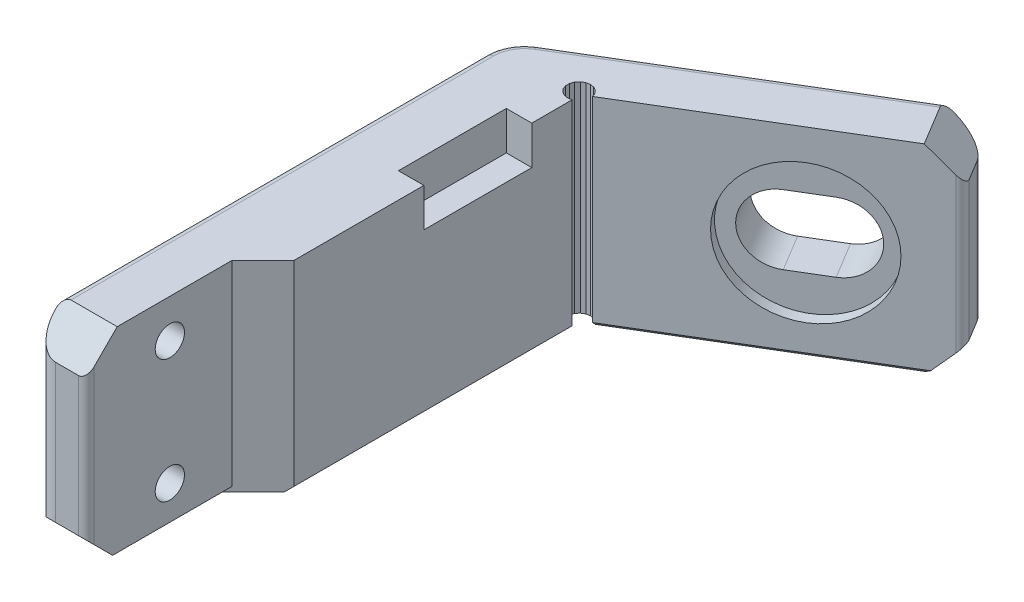
SolidWorks part; units mm, degrees
ref_plane "Front Plane" through (0, 0, 0) normal (0, 0, 1) x (1, 0, 0)
ref_plane "Top Plane" through (0, 0, 0) normal (0, 1, 0) x (1, 0, 0)
ref_plane "Right Plane" through (0, 0, 0) normal (1, 0, 0) x (0, 0, -1)
ref_plane "PY -20.700" through (0, -20.7, 0) normal (0, 1, 0) x (1, 0, 0)
sketch "leg and pad sketch" plane through (0, -20.7, 0) normal (0, 1, 0) x (1, 0, 0)
  line L0 (0.5513, 30.3327) -> (0.3673, 30.8194)
  line L1 (0.3673, 30.8194) -> (0.028, 31.2139)
  line L2 (0.028, 31.2139) -> (-0.4256, 31.4688)
  line L3 (-0.4256, 31.4688) -> (-0.939, 31.5534)
  line L4 (-0.939, 31.5534) -> (-1.4504, 31.4576)
  line L5 (-1.4504, 31.4576) -> (-1.8983, 31.1928)
  line L6 (-1.8983, 31.1928) -> (-2.2288, 30.7909)
  line L7 (-2.2288, 30.7909) -> (-2.4021, 30.3003)
  line L8 (-2.4021, 30.3003) -> (-2.3973, 29.78)
  line L9 (-2.3973, 29.78) -> (-2.2152, 29.2926)
  line L10 (-2.2152, 29.2926) -> (-1.8775, 28.8968)
  line L11 (-1.8775, 28.8968) -> (-1.4248, 28.6402)
  line L12 (-1.4248, 28.6402) -> (-0.9118, 28.5536)
  line L13 (-0.9118, 28.5536) -> (-0.4, 28.6475)
  line L14 (-0.4, 28.6475) -> (-0.4, -7.48)
  line L15 (-0.4, -7.48) -> (-4.42, -11.5)
  line L16 (-4.42, -11.5) -> (-4.42, -30.37)
  line L17 (-4.42, -30.37) -> (-11.42, -30.37)
  line L18 (-11.42, -30.37) -> (-11.42, 31.2838)
  line L19 (-11.42, 31.2838) -> (27.2048, 54.5947)
  line L20 (27.2048, 54.5947) -> (30.8218, 48.6015)
  line L21 (30.8218, 48.6015) -> (0.5513, 30.3327)
extrude "leg and pad" add sketch "leg and pad sketch" along normal mid plane 26
ref_plane "PX -1.350" through (-1.35, 0, 0) normal (1, 0, 0) x (0, 0, -1)
sketch "screw head relief sketch" plane through (-1.35, 0, 0) normal (1, 0, 0) x (0, 0, -1)
  line L0 (23.4, -12.7) -> (23.4, -6.7)
  line L1 (23.4, -6.7) -> (9.4, -6.7)
  line L2 (9.4, -6.7) -> (9.4, -12.7)
  line L3 (9.4, -12.7) -> (23.4, -12.7)
extrude "screw head relief" cut sketch "screw head relief sketch" against normal mid plane 4.7
sketch "insert flange relief sketch" plane through (0, -20.7, 0) normal (0, 1, 0) x (1, 0, 0)
  line L0 (18.3249, 39.8914) -> (17.0331, 42.0318)
  line L1 (17.0331, 42.0318) -> (9.3276, 37.3814)
  line L2 (9.3276, 37.3814) -> (10.6194, 35.241)
  line L3 (10.6194, 35.241) -> (18.3249, 39.8914)
revolve "insert flange relief" cut sketch "insert flange relief sketch" angle 360 about L0
sketch "M6 slot end 1 sketch" plane through (0, -20.7, 0) normal (0, 1, 0) x (1, 0, 0)
  line L0 (20.4653, 41.1832) -> (15.8149, 48.8886)
  line L1 (15.8149, 48.8886) -> (11.9621, 46.5634)
  line L2 (11.9621, 46.5634) -> (16.6125, 38.858)
  line L3 (16.6125, 38.858) -> (20.4653, 41.1832)
revolve "M6 slot end 1" cut sketch "M6 slot end 1 sketch" angle 360 about L0
sketch "M6 slot end 2 sketch" plane through (0, -20.7, 0) normal (0, 1, 0) x (1, 0, 0)
  line L0 (16.1845, 38.5996) -> (11.5341, 46.3051)
  line L1 (11.5341, 46.3051) -> (7.6813, 43.9799)
  line L2 (7.6813, 43.9799) -> (12.3317, 36.2744)
  line L3 (12.3317, 36.2744) -> (16.1845, 38.5996)
revolve "M6 slot end 2" cut sketch "M6 slot end 2 sketch" angle 360 about L0
sketch "M6 slot middle sketch" plane through (0, -20.7, 0) normal (0, 1, 0) x (1, 0, 0)
  line L0 (16.1845, 38.5996) -> (20.4653, 41.1832)
  line L1 (20.4653, 41.1832) -> (15.8149, 48.8886)
  line L2 (15.8149, 48.8886) -> (11.5341, 46.3051)
  line L3 (11.5341, 46.3051) -> (16.1845, 38.5996)
extrude "M6 slot middle" cut sketch "M6 slot middle sketch" against normal mid plane 9
ref_plane "PX -7.920" through (-7.92, 0, 0) normal (1, 0, 0) x (0, 0, -1)
sketch "screw holes sketch" plane through (-7.92, 0, 0) normal (1, 0, 0) x (0, 0, -1)
  circle A0 centre (-19.54, -28.7) radius 1.9
  circle A1 centre (-19.54, -12.7) radius 1.9
extrude "screw holes" cut sketch "screw holes sketch" against normal mid plane 9
chamfer "leg top corners" distance 4 angle 45 2 edges at (-7.92, -7.7, 30.37) (-7.92, -33.7, 30.37) tangent propagation no
chamfer "pad end corners" distance 4 angle 45 2 edges at (29.0133, -7.7, -51.5981) (29.0133, -33.7, -51.5981) tangent propagation no
fillet "outside of the bend" radius 5 1 edges at (-11.42, -20.7, -31.2838) tangent propagation no
fillet "leg top outer edge" radius 3 1 edges at (-11.42, -20.7, 30.37) tangent propagation no
fillet "pad end outer edge" radius 3 1 edges at (27.2048, -20.7, -54.5947) tangent propagation no
fillet "leg top inner edge" radius 1 1 edges at (-4.42, -20.7, 30.37) tangent propagation no
fillet "pad end inner edge" radius 1 1 edges at (30.8218, -20.7, -48.6015) tangent propagation no
chamfer "bed face chamfer" distance 0.6 angle 45 6 edges at (13.9742, -33.7, -38.4337) (7.3883, -33.7, -42.635) (-4.42, -33.7, 18.935) (-0.4, -33.7, -10.5837) (-10.7742, -33.7, -30.9193) (-11.42, -33.7, -1.0457)
fillet "top face edge" radius 1 3 edges at (7.3883, -7.7, -42.635) (-10.7742, -7.7, -30.9193) (-11.42, -7.7, -1.0457)
equation "\"diffL\"= 608.8mm"
equation "\"diffW\"= 329.4mm"
equation "\"diffT\"= 2.9mm"
equation "\"chanSlotW\"= 12.9mm"
equation "\"chanSlotDepth\"= 11.13mm"
equation "\"chanFloor\"= 1.57mm"
equation "\"chanLeg\"= 12.7mm"
equation "\"lightL\"= 605mm"
equation "\"lightW\"= 331mm"
equation "\"lightH\"= 92mm"
equation "\"lightSideFlat\"= 30mm"
equation "\"lightSlopeLen\"= 33.1mm"
equation "\"lightWingDepth\"= 47.9mm"
equation "\"lightWingFlat\"= 90.2mm"
equation "\"lightChanW\"= 99.6mm"
equation "\"lightChanStand\"= 44.1mm"
equation "\"insFlangeD\"= 12.3mm"
equation "\"insFromEnd\"= 20.7mm"
equation "\"insUpSlope\"= 20.8mm"
equation "\"gaugeH\"= 10mm"
equation "\"gaugeStepLen\"= 14mm"
equation "\"gaugeStepW0\"= 13.1mm"
equation "\"gaugeStepDW\"= 0.2mm"
equation "\"gaugeSteps\"= 5mm"
equation "\"gaugeHandleLen\"= 30mm"
equation "\"gaugeHandleW\"= 24mm"
equation "\"gaugeSlot0\"= 3mm"
equation "\"gaugeSlotD\"= 0.1mm"
equation "\"gaugeSlotDepth\"= 8mm"
equation "\"gap\"= 25.4mm"
equation "\"edgeL\"= 1mm"
equation "\"edgeW\"= 0.75mm"
equation "\"proud\"= 1.5mm"
equation "\"seatClr\"= 0.15mm"
equation "\"tongueClrZ\"= 0.1mm"
equation "\"tongueClrX\"= 0.25mm"
equation "\"tongueLen\"= 30mm"
equation "\"armSide\"= 45mm"
equation "\"armEnd\"= 20mm"
equation "\"cornerCham\"= 3mm"
equation "\"brkW\"= 26mm"
equation "\"brkT\"= 7mm"
equation "\"brkSeatClr\"= 0.2mm"
equation "\"brkScrewSpan\"= 16mm"
equation "\"pilotD\"= 2.7mm"
equation "\"pilotDepth\"= 10mm"
equation "\"screwClrD\"= 3.9mm"
equation "\"jogBelow\"= 4mm"
equation "\"padT\"= 7mm"
equation "\"padLen\"= 31mm"
equation "\"m6Clr\"= 7mm"
equation "\"m6Slot\"= 3mm"
equation "\"flangeRelD\"= 17mm"
equation "\"flangeRelDepth\"= 1.5mm"
equation "\"relLen\"= 7mm"
equation "\"relDepth\"= 4mm"
equation "\"relLand\"= 2mm"
equation "\"knockN\"= 100mm"
equation "\"petgcfE\"= 3000mm"
equation "\"mockExtent\"= 110mm"
equation "\"relZnear\"= 9.4mm"
equation "\"relZfar\"= 23.4mm"
equation "\"headD\"= 8mm"
equation "\"headH\"= 2.5mm"
equation "\"headFromEnd\"= 6.8mm"
equation "\"headBack\"= 16.4mm"
equation "\"sideClr\"= 0.4mm"
equation "\"cornerRelR\"= 1.5mm"
equation "\"cornerRelBack\"= 0.6mm"
equation "\"endHeadH\"= 2.8mm"
equation "\"footClr\"= 1.2mm"
equation "\"footEndClr\"= 3.5mm"
equation "\"footLift\"= 6mm"
equation "\"footBlockClr\"= 0.5mm"
equation "\"footBack\"= 50mm"
equation "\"footFwd\"= 10mm"
equation "\"footBraceEnd\"= 3mm"
equation "\"footLoadN\"= 25mm"
equation "\"spacerLen\"= 60mm"
equation "\"spacerShort\"= 0.5mm"
equation "\"spacerCham\"= 0.8mm"
equation "\"spacerPerSide\"= 3mm"
equation "\"spacerPerEnd\"= 1mm"
equation "\"toolR\"= 9mm"
equation "\"visR\"= 4mm"
equation "\"edgeR\"= 1mm"
equation "\"bendOutR\"= 5mm"
equation "\"insideR\"= 2.5mm"
equation "\"footCornerR\"= 10mm"
equation "\"footFrontR\"= 8mm"
equation "\"braceKinkR\"= 12mm"
equation "\"bedCham\"= 1mm"
equation "\"bedChamSmall\"= 0.6mm"
equation "\"soleTopR\"= 2mm"
equation "\"cornerR\"= 6mm"
equation "\"rimInR\"= 1mm"
equation "\"insFlangeH\"= 1mm"
equation "\"insHoleFinishD\"= 4.5mm"
equation "\"insLen\"= 6.4mm"
equation "\"footToeTip\" = 4mm"
equation "\"cgInset\" = 4mm"
equation "\"lampWeightN\" = 51mm"
equation "\"frameWeightN\" = 10mm"
equation "\"bumpIn\" = 8mm"
equation "\"bumpH\" = 3mm"
equation "\"legBelowFront\" = 2mm"
equation "\"lipClr\" = 0.1mm"
equation "\"revealR\" = 2mm"
equation "\"frontCham\" = 1mm"
